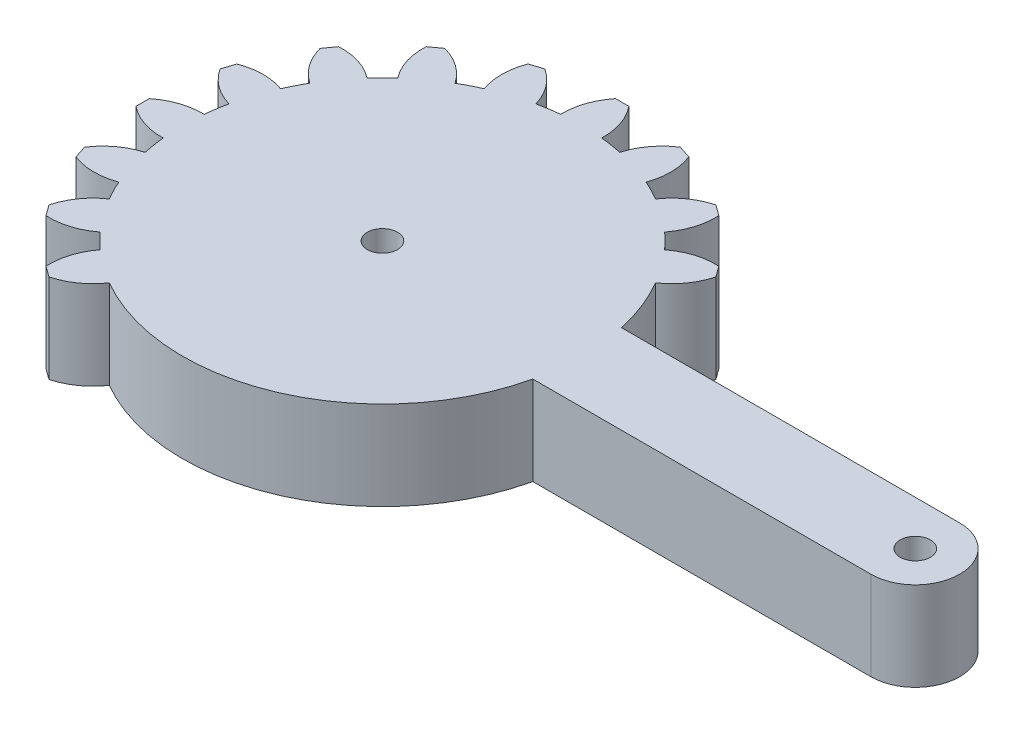
SolidWorks part; units mm, degrees
note: The reader was unsure of these and kept them because the rebuilt part matched: shared geometry of "Sketch2<7>".
ref_plane "Front Plane" through (0, 0, 0) normal (0, 0, 1) x (1, 0, 0)
ref_plane "Top Plane" through (0, 0, 0) normal (0, 1, 0) x (1, 0, 0)
ref_plane "Right Plane" through (0, 0, 0) normal (1, 0, 0) x (0, 0, -1)
sketch "Sketch2" plane through (0, 0, 0) normal (0, 1, 0) x (1, 0, 0)
  line L0 (0, 0) -> (60, 0) construction
  line L1 (0, 22.5) -> (0, -22.5) construction
  line L3 (60, 5) -> (60, -5) construction
  line L4 (60, 5) -> (21.9374, 5)
  line L5 (60, -5) -> (21.9374, -5)
  line L19 (0, 22.5) -> (0, 27) construction
  line L23 (0.75, 27) -> (-0.75, 27)
  line L24 (9.0568, 25.4468) -> (7.6302, 25.9103)
  line L25 (16.477, 21.4026) -> (15.2634, 22.2843)
  line L26 (22.2843, 15.2634) -> (21.4026, 16.477)
  line L27 (25.9103, 7.6302) -> (25.4468, 9.0568)
  line L28 (27, -0.75) -> (27, 0.75)
  line L29 (25.4468, -9.0568) -> (25.9103, -7.6302)
  line L30 (21.4026, -16.477) -> (22.2843, -15.2634)
  line L31 (15.2634, -22.2843) -> (16.477, -21.4026)
  line L32 (7.6302, -25.9103) -> (9.0568, -25.4468)
  line L33 (-0.75, -27) -> (0.75, -27)
  line L34 (-9.0568, -25.4468) -> (-7.6302, -25.9103)
  line L35 (-16.477, -21.4026) -> (-15.2634, -22.2843)
  line L36 (-22.2843, -15.2634) -> (-21.4026, -16.477)
  line L37 (-25.9103, -7.6302) -> (-25.4468, -9.0568)
  line L38 (-27, 0.75) -> (-27, -0.75)
  line L39 (-25.4468, 9.0568) -> (-25.9103, 7.6302)
  line L40 (-21.4026, 16.477) -> (-22.2843, 15.2634)
  line L41 (-15.2634, 22.2843) -> (-16.477, 21.4026)
  line L42 (-7.6302, 25.9103) -> (-9.0568, 25.4468)
  circle A1 centre (60, 0) radius 1.7
  arc A4 (60, 5) -> (60, -5) centre (60, 0) cw
  circle A5 centre (0, 0) radius 22.5
  arc A47 (-0.75, 27) -> (-2.3086, 22.3813) centre (4.6709, 22.5984) ccw
  arc A48 (0.75, 27) -> (2.3086, 22.3813) centre (-4.6709, 22.5984) cw
  arc A49 (7.6302, 25.9103) -> (4.7206, 21.9992) centre (11.4256, 20.049) ccw
  arc A50 (9.0568, 25.4468) -> (9.1118, 20.5724) centre (2.541, 22.9358) cw
  arc A51 (15.2634, 22.2843) -> (11.2877, 19.4638) centre (17.0618, 15.537) ccw
  arc A52 (16.477, 21.4026) -> (15.023, 16.7499) centre (9.5042, 21.028) cw
  arc A53 (21.4026, 16.477) -> (16.7499, 15.023) centre (21.028, 9.5042) ccw
  arc A54 (22.2843, 15.2634) -> (19.4638, 11.2877) centre (15.537, 17.0618) cw
  arc A55 (25.4468, 9.0568) -> (20.5724, 9.1118) centre (22.9358, 2.541) ccw
  arc A56 (25.9103, 7.6302) -> (21.9992, 4.7206) centre (20.049, 11.4256) cw
  arc A57 (27, 0.75) -> (22.3813, 2.3086) centre (22.5984, -4.6709) ccw
  arc A58 (27, -0.75) -> (22.3813, -2.3086) centre (22.5984, 4.6709) cw
  arc A59 (25.9103, -7.6302) -> (21.9992, -4.7206) centre (20.049, -11.4256) ccw
  arc A60 (25.4468, -9.0568) -> (20.5724, -9.1118) centre (22.9358, -2.541) cw
  arc A61 (22.2843, -15.2634) -> (19.4638, -11.2877) centre (15.537, -17.0618) ccw
  arc A62 (21.4026, -16.477) -> (16.7499, -15.023) centre (21.028, -9.5042) cw
  arc A63 (16.477, -21.4026) -> (15.023, -16.7499) centre (9.5042, -21.028) ccw
  arc A64 (15.2634, -22.2843) -> (11.2877, -19.4638) centre (17.0618, -15.537) cw
  arc A65 (9.0568, -25.4468) -> (9.1118, -20.5724) centre (2.541, -22.9358) ccw
  arc A66 (7.6302, -25.9103) -> (4.7206, -21.9992) centre (11.4256, -20.049) cw
  arc A67 (0.75, -27) -> (2.3086, -22.3813) centre (-4.6709, -22.5984) ccw
  arc A68 (-0.75, -27) -> (-2.3086, -22.3813) centre (4.6709, -22.5984) cw
  arc A69 (-7.6302, -25.9103) -> (-4.7206, -21.9992) centre (-11.4256, -20.049) ccw
  arc A70 (-9.0568, -25.4468) -> (-9.1118, -20.5724) centre (-2.541, -22.9358) cw
  arc A71 (-15.2634, -22.2843) -> (-11.2877, -19.4638) centre (-17.0618, -15.537) ccw
  arc A72 (-16.477, -21.4026) -> (-15.023, -16.7499) centre (-9.5042, -21.028) cw
  arc A73 (-21.4026, -16.477) -> (-16.7499, -15.023) centre (-21.028, -9.5042) ccw
  arc A74 (-22.2843, -15.2634) -> (-19.4638, -11.2877) centre (-15.537, -17.0618) cw
  arc A75 (-25.4468, -9.0568) -> (-20.5724, -9.1118) centre (-22.9358, -2.541) ccw
  arc A76 (-25.9103, -7.6302) -> (-21.9992, -4.7206) centre (-20.049, -11.4256) cw
  arc A77 (-27, -0.75) -> (-22.3813, -2.3086) centre (-22.5984, 4.6709) ccw
  arc A78 (-27, 0.75) -> (-22.3813, 2.3086) centre (-22.5984, -4.6709) cw
  arc A79 (-25.9103, 7.6302) -> (-21.9992, 4.7206) centre (-20.049, 11.4256) ccw
  arc A80 (-25.4468, 9.0568) -> (-20.5724, 9.1118) centre (-22.9358, 2.541) cw
  arc A81 (-22.2843, 15.2634) -> (-19.4638, 11.2877) centre (-15.537, 17.0618) ccw
  arc A82 (-21.4026, 16.477) -> (-16.7499, 15.023) centre (-21.028, 9.5042) cw
  arc A83 (-16.477, 21.4026) -> (-15.023, 16.7499) centre (-9.5042, 21.028) ccw
  arc A84 (-15.2634, 22.2843) -> (-11.2877, 19.4638) centre (-17.0618, 15.537) cw
  arc A85 (-9.0568, 25.4468) -> (-9.1118, 20.5724) centre (-2.541, 22.9358) ccw
  arc A86 (-7.6302, 25.9103) -> (-4.7206, 21.9992) centre (-11.4256, 20.049) cw
  point P7 (0, 0)
  point P18 (60, 0)
  point P21 (0, 27.0653)
  point P137 (0, 0)
  point P162 (0, 0)
  dimension "D1" = 45
  dimension "D3" = 3.4
  dimension "D4" = 1.5
  dimension "D2" = 60
  dimension "D5" = 20
  dimension "D6" = 10
  dimension "D7" = 4.5
extrude "Boss-Extrude1" add sketch "Sketch2" along normal blind 10
extrude "Boss-Extrude2" add sketch "Sketch2<7>" along normal blind 10
sketch "Sketch2<7>" plane through (0, 0, 0) normal (0, 1, 0) x (1, 0, 0) same geometry as "Sketch2"
sketch "Sketch3" plane through (0, 10, 0) normal (0, 1, 0) x (1, 0, 0)
  circle A0 centre (0, 0) radius 1.7
  dimension "D1" = 3.4
extrude "Cut-Extrude1" cut sketch "Sketch3" against normal through all
